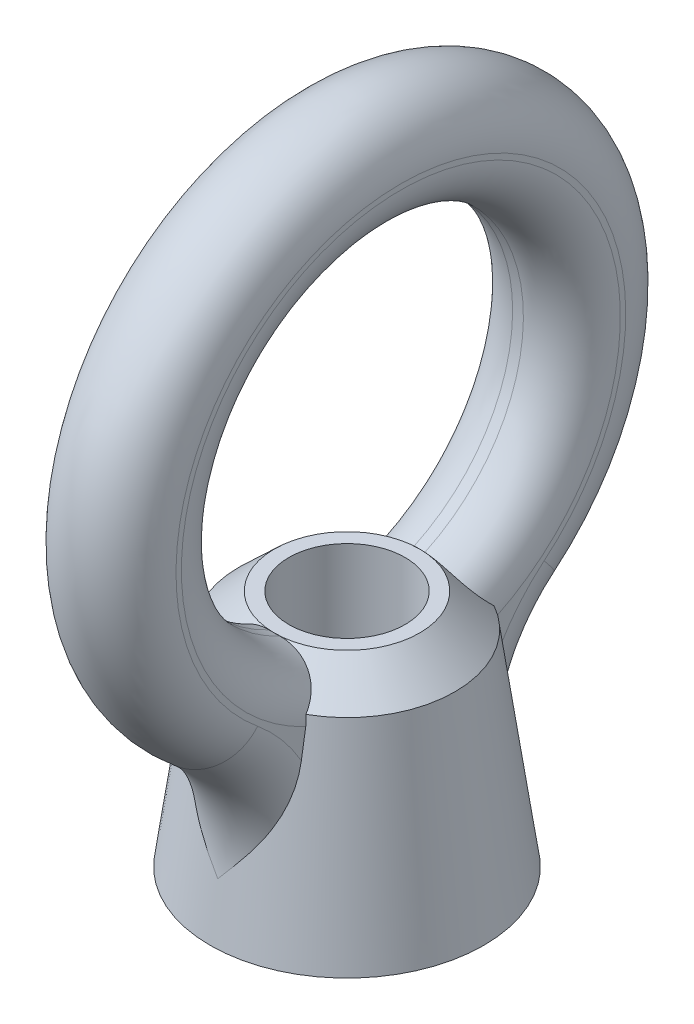
SolidWorks part; units mm, degrees
ref_plane "Front Plane" through (0, 0, 0) normal (0, 0, 1) x (1, 0, 0)
ref_plane "Top Plane" through (0, 0, 0) normal (0, 1, 0) x (1, 0, 0)
ref_plane "Right Plane" through (0, 0, 0) normal (1, 0, 0) x (0, 0, -1)
sketch "RingSke" plane through (0, 0, 0) normal (1, 0, 0) x (0, 0, -1)
  line L0 (-6.8465, -14.7924) -> (-7.7751, -21.4)
  line L1 (-8, -23) -> (8, -23) construction
  line L2 (7.7751, -21.4) -> (6.8465, -14.7924)
  line L3 (0, -42.7525) -> (0, 122.379) construction
  line L4 (7.7751, -21.4) -> (-7.7751, -21.4)
  line L5 (7.7751, -21.4) -> (8, -23) construction
  line L6 (-7.7751, -21.4) -> (-8, -23) construction
  arc A0 (6.8465, -14.7924) -> (-6.8465, -14.7924) centre (0, 0) ccw
  circle A1 centre (0, 0) radius 10
  dimension "D4" = 82
  dimension "Height" = 23
extrude "Ring" add sketch "RingSke" along normal mid plane 6.3
fillet "NutFillet" radius 8 2 edges at (0, -14.7924, -6.8465) (0, -14.7924, 6.8465)
fillet "Fillet1" 10 edges at (3.15, -20.6228, -7.6659) (3.15, -15.8371, -8.0211) (3.15, 16.3, 0) (3.15, -15.8371, 8.0211) (3.15, -20.6228, 7.6659) (-3.15, -20.6228, 7.6659) (-3.15, -15.8371, 8.0211) (-3.15, 16.3, 0) (-3.15, -15.8371, -8.0211) (-3.15, -20.6228, -7.6659) type full round first side face at (3.15, -13.0033, 0) second side face at (-3.15, -13.0033, 0) middle face at (0, -20.6228, -7.6659) middle face at (0, -16.0213, -8.4954) middle face at (0, 1.8674, 0) middle face at (0, -16.0213, 8.4954) middle face at (0, -20.6228, 7.6659)
sketch "BaseNutSke" plane through (0, 0, 0) normal (0, 0, 1) x (1, 0, 0)
  line L0 (0, 31.5203) -> (0, -191.7139) construction
  line L1 (0, -9.0519) -> (-4.25, -9.0519)
  line L2 (-4.25, -9.0519) -> (-6.3135, -11)
  line L3 (-6.3135, -11) -> (-8, -23)
  line L4 (-8, -23) -> (-4.25, -23)
  line L5 (0, -21.4) -> (0, -9.0519)
  line L6 (-4.25, -23) -> (-1.4787, -21.4)
  line L7 (-1.4787, -21.4) -> (0, -21.4)
  dimension "D1" = 82
  dimension "Height" = 23
  dimension "D4" = 60
  dimension "D7" = 10
fillet "Fillet2" radius 2.835 2 edges at (3.15, 0, -10) (-3.15, 0, -10)
revolve "BaseNut" add sketch "BaseNutSke" angle 360 about L0
sketch "HoleSke" plane through (0, -9.0519, 0) normal (0, 1, 0) x (1, 0, 0)
  circle A0 centre (0, 0) radius 3.4
  dimension "Tap_drill" = 6.8
extrude "TappedHole" cut sketch "HoleSke" against normal through all
cosmetic thread "ThreadCosmetic" [suppressed] parameters "Thread_major"=8
sketch "ThdSchSke" plane through (0, 0, 0) normal (0, 0, 1) x (1, 0, 0)
  line L0 (-3.4, -21.8164) -> (-4, -22.1628)
  line L1 (-4, -22.1628) -> (-3.4, -22.5093)
  line L2 (-3.4, -22.5093) -> (-2.7072, -22.5093)
  line L3 (-2.7072, -22.5093) -> (-2.7072, -21.8164)
  line L4 (-2.7072, -21.8164) -> (-3.4, -21.8164)
  line L7 (0, 0) -> (0, -34.0579) construction
  line L9 (3.4, -22.5093) -> (-3.4, -22.5093) construction
  dimension "Tap_drill" = 6.8
revolve "ThreadSchematic" [suppressed] cut sketch "ThdSchSke" angle 360 about L7
pattern_linear "ThdSchPat" [suppressed] of bodies 110
equation "\"Bottom_height@RingSke\" = \"Bottom_Width@RingSke\"/10"
equation "\"Ring_thickness@Ring\" =  ( \"Ring_diameterA@RingSke\" - \"Ring_diameterB@RingSke\" ) / 2 "
equation "\"D1@Fillet2\" = \"Ring_thickness@Ring\" * 0.45"
equation "\"Height@BaseNutSke\" = \"Height@RingSke\""
equation "\"Chamfer_height@BaseNutSke\" = \"Bottom_height@RingSke\""
equation "\"Bottom_width@BaseNutSke\" = \"Bottom_Width@RingSke\""
equation "\"D7@BaseNutSke\" = \"Ring_diameterB@RingSke\"/2"
equation "\"Tap_drill@ThdSchSke\" = \"Tap_drill@HoleSke\""
equation "\"ThreadN@ThdSchSke\" = \"Thread_major@ThreadCosmetic\""
equation "\"Num_threads@ThdSchPat\" =  int( \"Height@RingSke\" / \"Advance@ThdSchPat\" ) "
